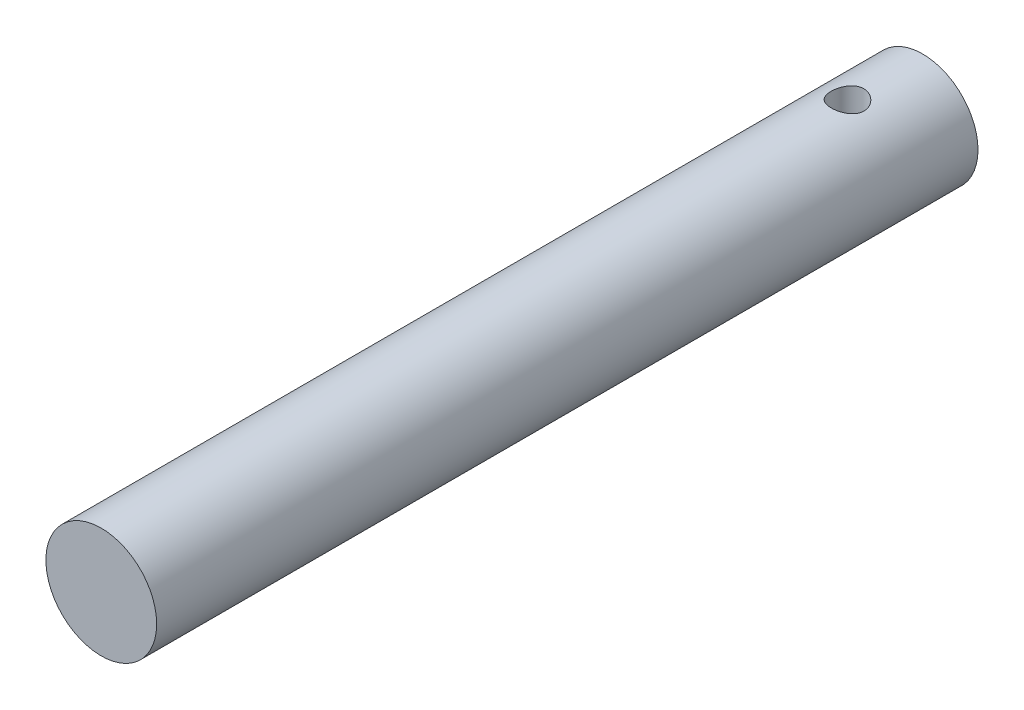
SolidWorks part; units mm, degrees
ref_plane "Front Plane" through (0, 0, 0) normal (0, 0, 1) x (1, 0, 0)
ref_plane "Top Plane" through (0, 0, 0) normal (0, 1, 0) x (1, 0, 0)
ref_plane "Right Plane" through (0, 0, 0) normal (1, 0, 0) x (0, 0, -1)
sketch "Sketch3" plane through (0, 0, 0) normal (0, 0, 1) x (1, 0, 0)
  circle A0 centre (0, 0) radius 6
extrude "Boss-Extrude1" add sketch "Sketch3" along normal blind 89
sketch "Sketch4" plane through (0, 0, 0) normal (0, 1, 0) x (1, 0, 0)
  line L0 (0, 0) -> (0, -50000) construction
  circle A0 centre (0.0962, -8.2368) radius 1.7875
  circle A1 centre (0, -123.2368) radius 2
  dimension "D1" = 115
extrude "Cut-Extrude1" cut sketch "Sketch4" against normal through all
extrude "Cut-Extrude2" cut sketch "Sketch4<2>" along normal through all
sketch "Sketch4<2>" plane through (0, 0, 0) normal (0, 1, 0) x (1, 0, 0) same geometry as "Sketch4"
